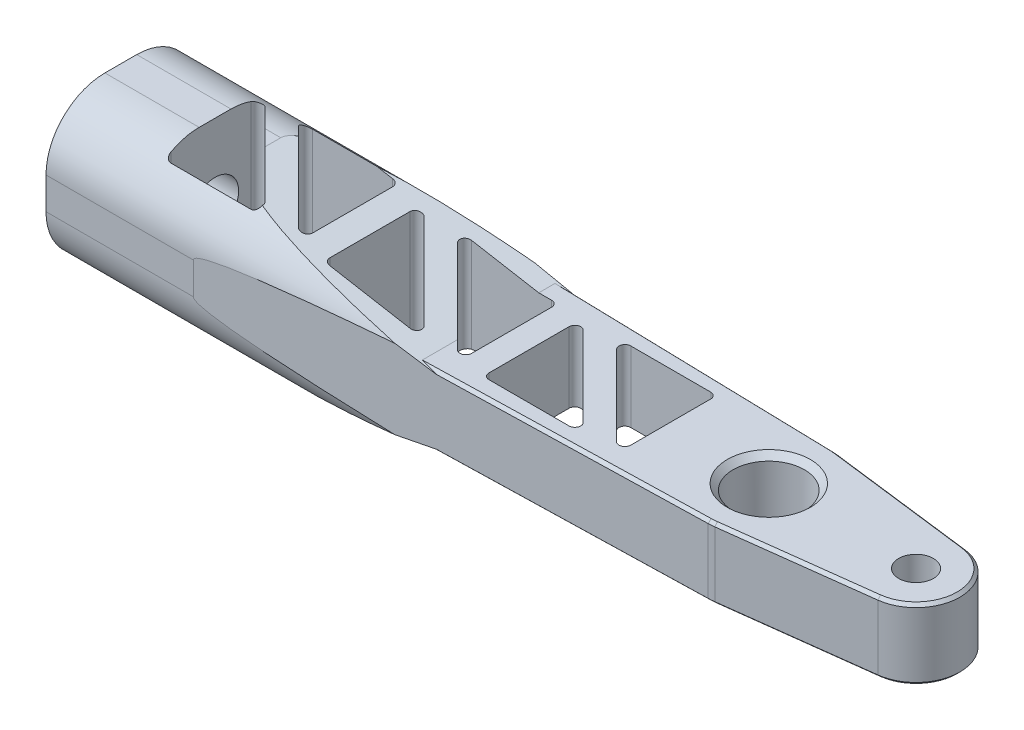
SolidWorks part; units mm, degrees
ref_plane "Front Plane" through (0, 0, 0) normal (0, 0, 1) x (1, 0, 0)
ref_plane "Top Plane" through (0, 0, 0) normal (0, 1, 0) x (1, 0, 0)
ref_plane "Right Plane" through (0, 0, 0) normal (1, 0, 0) x (0, 0, -1)
sketch "Sketch1" plane through (0, 0, 0) normal (0, 1, 0) x (1, 0, 0)
  line L1 (-67.5, -12.7) -> (67.5, -12.7)
  line L2 (-67.5, -12.7) -> (-67.5, 12.7)
  line L3 (-67.5, 12.7) -> (67.5, 12.7)
  line L5 (-67.5, -12.7) -> (67.5, 12.7) construction
  line L6 (-67.5, 12.7) -> (67.5, -12.7) construction
  arc A0 (67.5, -12.7) -> (67.5, 12.7) centre (67.5, 0) ccw
  circle A1 centre (67.5, 0) radius 2.95
  circle A2 centre (42.5, 0) radius 6.05
  point P0 (0, 0)
  dimension "D4" = 12.1
  dimension "D5" = 5.9
  dimension "D1" = 25.4
  dimension "D2" = 110
  dimension "D3" = 25
extrude "Boss-Extrude1" add sketch "Sketch1" along normal blind 12.7 and the other way blind 12.7 contours A2 | A1 | L3 A0 L1 L2 region at (67.5, 0, 0) region at (42.5, 0, 0)
sketch "Sketch6" plane through (0, 12.7, 0) normal (0, 1, 0) x (1, 0, 0)
  line L1 (-67.5, -12.7) -> (67.5, -12.7) construction
  line L4 (43.8082, -10.4686) -> (68.4238, -7.3925)
  line L6 (-67.5, 12.7) -> (67.5, 12.7) construction
  line L7 (-67.5, -12.7) -> (67.5, -12.7)
  line L8 (43.8082, 10.4686) -> (68.4238, 7.3925)
  line L9 (-67.5, 12.7) -> (67.5, 12.7)
  line L10 (42.7664, 10.5466) -> (-42.5, 12.7)
  line L11 (42.7664, -10.5466) -> (-42.5, -12.7)
  line L12 (-67.5, -12.7) -> (-67.5, 12.7) construction
  arc A4 (67.5, -12.7) -> (67.5, 12.7) centre (67.5, 0) ccw construction
  arc A5 (67.5, -12.7) -> (67.5, 12.7) centre (67.5, 0) ccw
  circle A10 centre (42.5, 0) radius 10.55
  circle A11 centre (42.5, 0) radius 10.55
  circle A13 centre (67.5, 0) radius 7.45
  circle A14 centre (67.5, 0) radius 7.45
  arc M8 (67.5, -12.7) -> (67.5, 12.7) centre (67.5, 0) ccw
  line M9 (67.5, 12.7) -> (-67.5, 12.7)
  dimension "D3" = 25
  dimension "D1" = 4.5
  dimension "D2" = 4.5
extrude "Cut-Extrude4" cut sketch "Sketch6" against normal through all contours A14 L4 A11 L11 L7 L10 L8 M8 M9 region at (56.2714, 12.7, 10.1739)
sketch "Sketch2" plane through (0, 0, -12.7) normal (0, 0, -1) x (-1, 0, 0)
  line L0 (67.5, -12.7) -> (42.5, -12.7) construction
  line L1 (-74.95, 12.7) -> (43.0476, 12.7)
  line L2 (-74.95, 12.7) -> (-74.95, 6)
  line L3 (-74.95, 6) -> (5.05, 6)
  line L5 (-74.95, -12.7) -> (43.0476, -12.7)
  line L6 (-74.95, -12.7) -> (-74.95, -6)
  line L7 (-74.95, -6) -> (5.05, -6)
  line L9 (67.5, 12.7) -> (42.5, 12.7) construction
  line L10 (5.05, 6) -> (43.0476, 12.7)
  line L11 (5.05, -6) -> (43.0476, -12.7)
  line L13 (-74.95, 12.7) -> (-74.95, -12.7) construction
  dimension "D1" = 12
  dimension "D2" = 10
  dimension "D3" = 10
  dimension "D4" = 80
extrude "Cut-Extrude1" cut sketch "Sketch2" against normal through all
fillet "Fillet8" radius 10 4 edges at (-55.2738, -12.7, 12.7) (-55.2738, 12.7, 12.7) (-55.2738, -12.7, -12.7) (-55.2738, 12.7, -12.7)
sketch "Sketch7" plane through (0, 12.7, 0) normal (0, 1, 0) x (1, 0, 0)
  line L0 (-51.5, 8.5) -> (-51.5, -8.5)
  line L1 (-51.5, -8.5) -> (-34.5, -8.5)
  line L2 (-34.5, -8.5) -> (-51.5, 8.5)
  line L3 (-45.8431, 8.5) -> (-28.8431, -8.5)
  line L4 (-28.8431, -8.5) -> (-28.8431, 8.5)
  line L5 (-28.8431, 8.5) -> (-45.8431, 8.5)
  line L6 (-67.5, -2.7) -> (-67.5, 2.7) construction
  point P5 (-51.5, 0)
  point P10 (-28.8431, 0)
  dimension "D1" = 17
  dimension "D2" = 16
  dimension "D3" = 4
extrude "Cut-Extrude5" cut sketch "Sketch7" against normal through all
ref_axis "Axis2" through (81.6525, 0, 0) along (-1, 0, 0)
fillet "Fillet9" radius 1 6 edges at (-28.8431, 0, -8.5) (-45.8431, 0, -8.5) (-28.8431, 0, 8.5) (-34.5, 0, 8.5) (-51.5, 0, -8.5) (-51.5, 0, 8.5)
pattern_linear "LPattern1" count 3 spacing 27 along (1, 0, 0) of "Cut-Extrude5", "Fillet9"
chamfer "Chamfer2" distance 0.5 angle 45 14 edges at (18.8582, -6, 11.1504) (43.2882, -6, 10.5205) (56.116, -6, 8.9305) (18.8582, -6, -11.1504) (74.95, -6, 0) (43.2882, -6, -10.5205) (56.116, -6, -8.9305) (18.8582, 6, 11.1504) (43.2882, 6, 10.5205) (56.116, 6, 8.9305) (74.95, 6, 0) (56.116, 6, -8.9305) (43.2882, 6, -10.5205) (18.8582, 6, -11.1504)
sketch "Sketch8" plane through (-67.5, 0, 0) normal (-1, 0, 0) x (0, 0, 1)
  circle A0 centre (0, 0) radius 4
  dimension "D1" = 8
extrude "Cut-Extrude6" cut sketch "Sketch8" against normal blind 18
chamfer "Chamfer3" distance 1 angle 45 1 edges at (42.5, 6, -6.05)
ref_plane "Plane1" [suppressed] through (0, -12.7, 0) normal (0, -1, 0) x (-1, 0, 0)
mirror "Mirror1" [suppressed] about plane through (0, -12.7, 0) normal (0, -1, 0) of bodies 110
delete or keep bodies "Body-Delete/Keep 1" [suppressed] type delete bodies bodies 110
equation "\"D1@Fillet7\"=40mm"
